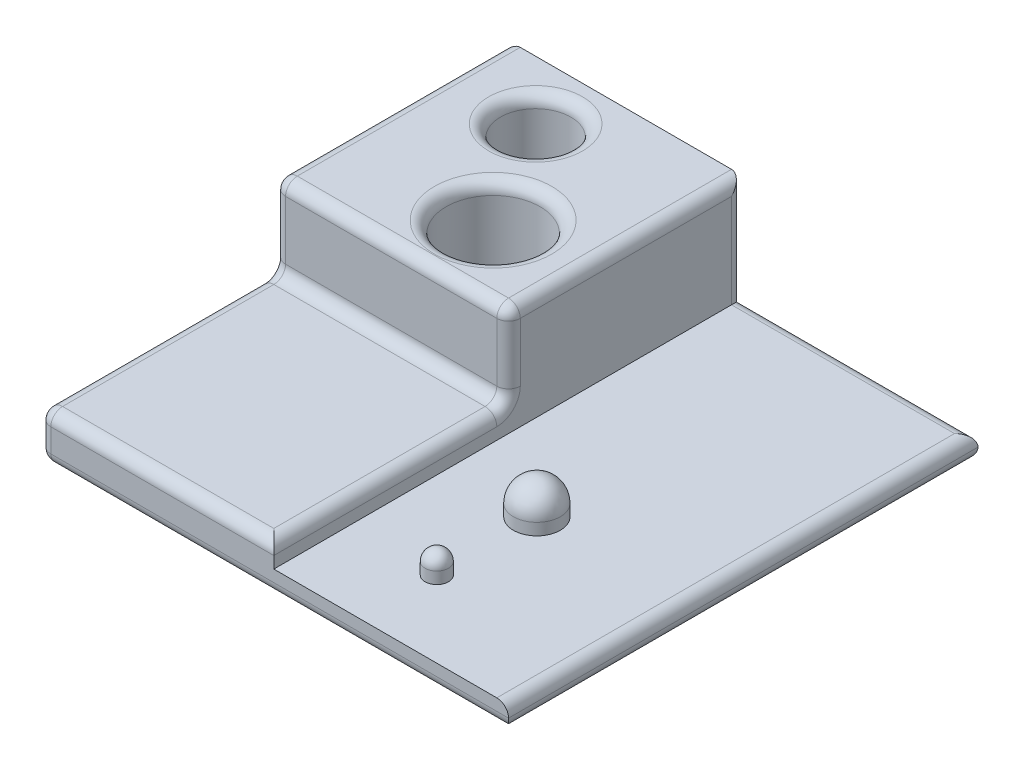
SolidWorks part; units mm, degrees
ref_plane "Front Plane" through (0, 0, 0) normal (0, 0, 1) x (1, 0, 0)
ref_plane "Top Plane" through (0, 0, 0) normal (0, 1, 0) x (1, 0, 0)
ref_plane "Right Plane" through (0, 0, 0) normal (1, 0, 0) x (0, 0, -1)
sketch "Sketch1" plane through (0, 0, 0) normal (0, 1, 0) x (1, 0, 0)
  line L1 (0, 0) -> (10, 0)
  line L2 (0, 0) -> (0, 20)
  line L3 (0, 20) -> (10, 20)
  line L4 (10, 0) -> (10, 20)
  dimension "D1" = 10
  dimension "D2" = 20
extrude "Boss-Extrude1" add sketch "Sketch1" along normal blind 2
sketch "Sketch2" plane through (0, 0, 0) normal (0, 1, 0) x (1, 0, 0)
  line L1 (10, 0) -> (20, 0)
  line L2 (10, 0) -> (10, 20)
  line L3 (10, 20) -> (20, 20)
  line L4 (20, 0) -> (20, 20)
  dimension "D1" = 20
  dimension "D2" = 10
extrude "Boss-Extrude2" add sketch "Sketch2" along normal blind 1
sketch "Sketch3" plane through (0, 1, 0) normal (0, 1, 0) x (1, 0, 0)
  circle A0 centre (13.6915, 3.2527) radius 0.5
extrude "Boss-Extrude3" add sketch "Sketch3" along normal blind 1
fillet "Fillet1" radius 0.5 1 edges at (13.6915, 2, -2.7527)
sketch "Sketch4" plane through (0, 1, 0) normal (0, 1, 0) x (1, 0, 0)
  circle A0 centre (13.673, 7.5339) radius 1
extrude "Boss-Extrude4" add sketch "Sketch4" along normal blind 1.5
fillet "Fillet2" radius 1 1 edges at (13.673, 2.5, -6.5339)
sketch "Sketch5" plane through (0, 2, 0) normal (0, 1, 0) x (1, 0, 0)
  line L0 (10, 0) -> (10, 20) construction
  line L1 (0, 20) -> (10, 20)
  line L2 (0, 20) -> (0, 10)
  line L3 (0, 10) -> (10, 10)
  line L4 (10, 20) -> (10, 10)
extrude "Boss-Extrude5" add sketch "Sketch5" along normal blind 3.5
sketch "Sketch7" plane through (0, 5.5, 0) normal (0, 1, 0) x (1, 0, 0)
  circle A0 centre (3.651, 17.5033) radius 1.5
extrude "Cut-Extrude1" cut sketch "Sketch7" against normal blind 4
sketch "Sketch8" plane through (0, 5.5, 0) normal (0, 1, 0) x (1, 0, 0)
  circle A0 centre (6.3008, 13.0433) radius 2
extrude "Cut-Extrude2" cut sketch "Sketch8" against normal blind 5
fillet "Fillet3" radius 0.5 20 edges at (0, 2, -5) (20, 0, -10) (20, 1, -10) (10, 0, -20) (0, 0, -10) (10, 0, 0) (0, 1, 0) (5, 2, 0) (5, 2, -10) (10, 2, -5) (15, 1, -20) (0, 2.75, -20) (10, 3.25, -20) (10, 5.5, -15) (10, 3.75, -10) (0, 3.75, -10) (0, 5.5, -15) (5, 5.5, -10) (6.3008, 5.5, -11.0433) (3.651, 5.5, -16.0033)
